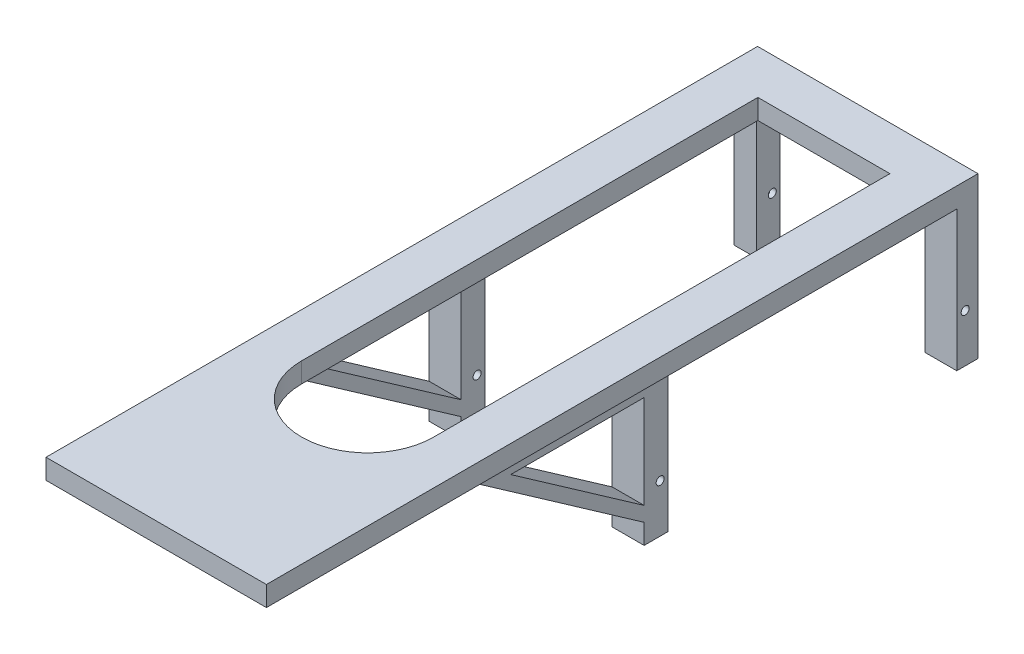
SolidWorks part; units mm, degrees
ref_plane "Plan de face" through (0, 0, 0) normal (0, 0, 1) x (1, 0, 0)
ref_plane "Plan de dessus" through (0, 0, 0) normal (0, 1, 0) x (1, 0, 0)
ref_plane "Plan de droite" through (0, 0, 0) normal (1, 0, 0) x (0, 0, -1)
sketch "Esquisse2" plane through (0, 0, 0) normal (0, 1, 0) x (1, 0, 0)
  line L0 (63.173, 102.455) -> (55.173, 102.455)
  line L1 (13.713, 101.825) -> (8.113, 101.825)
  line L2 (13.713, 101.825) -> (13.713, 107.755)
  line L3 (13.713, 107.755) -> (8.113, 107.755)
  line L4 (8.113, 101.825) -> (8.113, 107.755)
  line L5 (13.713, 101.825) -> (8.113, 107.755) construction
  line L6 (13.713, 107.755) -> (8.113, 101.825) construction
  line L7 (63.173, 102.455) -> (63.173, 107.755)
  line L8 (63.173, 107.755) -> (55.173, 107.755)
  line L9 (55.173, 102.455) -> (55.173, 107.755)
  line L10 (16.183, 25.625) -> (8.183, 25.625)
  line L11 (16.183, 25.625) -> (16.183, 31.625)
  line L12 (16.183, 31.625) -> (8.183, 31.625)
  line L13 (8.183, 25.625) -> (8.183, 31.625)
  line L14 (61.903, 25.625) -> (53.903, 25.625)
  line L15 (61.903, 25.625) -> (61.903, 31.625)
  line L16 (61.903, 31.625) -> (53.903, 31.625)
  line L17 (53.903, 25.625) -> (53.903, 31.625)
  circle A0 centre (12.183, 29.625) radius 1.6 construction
  circle A1 centre (57.903, 29.625) radius 1.6 construction
  circle A2 centre (10.913, 105.825) radius 1.6 construction
  circle A3 centre (59.173, 104.555) radius 1.6 construction
  point P8 (10.913, 104.79)
  dimension "D1" = 3.2
  dimension "D2" = 3.2
  dimension "D3" = 3.2
  dimension "D4" = 3.2
  dimension "D5" = 12.183
  dimension "D6" = 29.625
  dimension "D7" = 57.903
  dimension "D8" = 29.625
  dimension "D9" = 10.913
  dimension "D10" = 105.825
  dimension "D11" = 59.173
  dimension "D12" = 104.555
  dimension "D14" = 4
  dimension "D15" = 2.8
  dimension "D16" = 2.8
  dimension "D17" = 2.1
  dimension "D18" = 3.2
  dimension "D19" = 4
  dimension "D20" = 4
  dimension "D21" = 4
  dimension "D22" = 2
  dimension "D23" = 4
  dimension "D24" = 4
  dimension "D25" = 8
  dimension "D26" = 4
  dimension "D27" = 2
  dimension "D28" = 4
extrude "Boss.-Extru.1" add sketch "Esquisse2" along normal blind 35
ref_plane "Plan1" through (0, 35, 0) normal (0, 1, 0) x (1, 0, 0)
sketch "Esquisse3" plane through (0, 35, 0) normal (0, 1, 0) x (1, 0, 0)
  line L0 (13.713, 107.755) -> (8.113, 107.755) construction
  line L1 (63.173, -70) -> (8.113, -70)
  line L2 (63.173, -70) -> (63.173, 107.755)
  line L3 (63.173, 107.755) -> (8.113, 107.755)
  line L4 (8.113, -70) -> (8.113, 107.755)
  line L5 (63.173, -70) -> (8.113, 107.755) construction
  line L6 (63.173, 107.755) -> (8.113, -70) construction
  line L7 (8.113, 107.755) -> (8.113, 101.825) construction
  line L8 (63.173, 102.455) -> (63.173, 107.755) construction
  point P0 (35.643, 18.8775)
  dimension "D1" = 0
  dimension "D2" = 0
  dimension "D3" = 0
  dimension "D4" = 70
extrude "Boss.-Extru.2" add sketch "Esquisse3" along normal blind 5
ref_plane "Plan2" through (0, 0, -107.755) normal (0, 0, -1) x (-1, 0, 0)
sketch "Esquisse8" plane through (0, 35, 0) normal (0, 1, 0) x (1, 0, 0)
  line L0 (8.113, -70) -> (63.173, -70) construction
  line L1 (54.673, -69) -> (55.173, -69)
  line L2 (54.673, -69) -> (54.673, -44)
  line L3 (54.673, -44) -> (55.173, -44)
  line L4 (55.173, -69) -> (55.173, -44)
  line L5 (54.673, -69) -> (55.173, -44) construction
  line L6 (54.673, -44) -> (55.173, -69) construction
  line L7 (60.173, -69) -> (60.673, -69)
  line L8 (60.173, -69) -> (60.173, -44)
  line L9 (60.173, -44) -> (60.673, -44)
  line L10 (60.673, -69) -> (60.673, -44)
  line L11 (60.173, -69) -> (60.673, -44) construction
  line L12 (60.173, -44) -> (60.673, -69) construction
  line L26 (63.173, -70) -> (63.173, 102.455) construction
  line L27 (49.173, -69) -> (49.673, -69)
  line L28 (49.173, -69) -> (49.173, -44)
  line L29 (49.173, -44) -> (49.673, -44)
  line L30 (49.673, -69) -> (49.673, -44)
  line L31 (49.173, -69) -> (49.673, -44) construction
  line L32 (49.173, -44) -> (49.673, -69) construction
  line L33 (43.673, -69) -> (44.173, -69)
  line L34 (43.673, -69) -> (43.673, -44)
  line L35 (43.673, -44) -> (44.173, -44)
  line L36 (44.173, -69) -> (44.173, -44)
  line L37 (43.673, -69) -> (44.173, -44) construction
  line L38 (43.673, -44) -> (44.173, -69) construction
  line L39 (38.173, -69) -> (38.673, -69)
  line L40 (38.173, -69) -> (38.173, -44)
  line L41 (38.173, -44) -> (38.673, -44)
  line L42 (38.673, -69) -> (38.673, -44)
  line L43 (38.173, -69) -> (38.673, -44) construction
  line L44 (38.173, -44) -> (38.673, -69) construction
  line L45 (32.673, -69) -> (33.173, -69)
  line L46 (32.673, -69) -> (32.673, -44)
  line L47 (32.673, -44) -> (33.173, -44)
  line L48 (33.173, -69) -> (33.173, -44)
  line L49 (32.673, -69) -> (33.173, -44) construction
  line L50 (32.673, -44) -> (33.173, -69) construction
  line L51 (27.173, -69) -> (27.673, -69)
  line L52 (27.173, -69) -> (27.173, -44)
  line L53 (27.173, -44) -> (27.673, -44)
  line L54 (27.673, -69) -> (27.673, -44)
  line L55 (27.173, -69) -> (27.673, -44) construction
  line L56 (27.173, -44) -> (27.673, -69) construction
  line L57 (21.673, -69) -> (22.173, -69)
  line L58 (21.673, -69) -> (21.673, -44)
  line L59 (21.673, -44) -> (22.173, -44)
  line L60 (22.173, -69) -> (22.173, -44)
  line L61 (21.673, -69) -> (22.173, -44) construction
  line L62 (21.673, -44) -> (22.173, -69) construction
  line L63 (16.173, -69) -> (16.673, -69)
  line L64 (16.173, -69) -> (16.173, -44)
  line L65 (16.173, -44) -> (16.673, -44)
  line L66 (16.673, -69) -> (16.673, -44)
  line L67 (16.173, -69) -> (16.673, -44) construction
  line L68 (16.173, -44) -> (16.673, -69) construction
  line L69 (10.673, -69) -> (11.173, -69)
  line L70 (10.673, -69) -> (10.673, -44)
  line L71 (10.673, -44) -> (11.173, -44)
  line L72 (11.173, -69) -> (11.173, -44)
  line L73 (10.673, -69) -> (11.173, -44) construction
  line L74 (10.673, -44) -> (11.173, -69) construction
  point P0 (54.923, -56.5)
  point P5 (60.423, -56.5)
  point P10 (0, 0)
  point P23 (49.423, -56.5)
  point P30 (43.923, -56.5)
  point P35 (38.423, -56.5)
  point P40 (32.923, -56.5)
  point P45 (27.423, -56.5)
  point P50 (21.923, -56.5)
  point P55 (16.423, -56.5)
  point P60 (10.923, -56.5)
  dimension "D1" = 0.5
  dimension "D2" = 0.5
  dimension "D5" = 25
  dimension "D6" = 25
  dimension "D9" = 1
  dimension "D10" = 1
  dimension "D11" = 5
  dimension "D12" = 2.5
  dimension "D13" = 9
  dimension "D16" = 5
extrude "Enlèv. mat.-Extru.3" cut sketch "Esquisse8" along normal blind 3.5
sketch "Esquisse9" plane through (0, 35, 0) normal (0, 1, 0) x (1, 0, 0)
  line L0 (63.173, -70) -> (63.173, 102.455) construction
  line L1 (37.173, -65) -> (62.173, -65)
  line L2 (37.173, -65) -> (37.173, -64.5)
  line L3 (37.173, -64.5) -> (62.173, -64.5)
  line L4 (62.173, -65) -> (62.173, -64.5)
  line L5 (37.173, -65) -> (62.173, -64.5) construction
  line L6 (37.173, -64.5) -> (62.173, -65) construction
  line L7 (8.113, -70) -> (63.173, -70) construction
  line L8 (9.113, -65) -> (34.113, -65)
  line L9 (9.113, -65) -> (9.113, -64.5)
  line L10 (9.113, -64.5) -> (34.113, -64.5)
  line L11 (34.113, -65) -> (34.113, -64.5)
  line L12 (9.113, -65) -> (34.113, -64.5) construction
  line L13 (9.113, -64.5) -> (34.113, -65) construction
  line L14 (8.113, 101.825) -> (8.113, -70) construction
  line L15 (37.173, -62) -> (62.173, -62)
  line L16 (37.173, -62) -> (37.173, -61.5)
  line L17 (37.173, -61.5) -> (62.173, -61.5)
  line L18 (62.173, -62) -> (62.173, -61.5)
  line L19 (9.113, -62) -> (34.113, -62)
  line L20 (9.113, -62) -> (9.113, -61.5)
  line L21 (9.113, -61.5) -> (34.113, -61.5)
  line L22 (34.113, -62) -> (34.113, -61.5)
  line L23 (37.173, -62) -> (62.173, -61.5) construction
  line L24 (37.173, -61.5) -> (62.173, -62) construction
  line L25 (9.113, -62) -> (34.113, -61.5) construction
  line L26 (9.113, -61.5) -> (34.113, -62) construction
  line L27 (37.173, -59) -> (62.173, -59)
  line L28 (37.173, -59) -> (37.173, -58.5)
  line L29 (37.173, -58.5) -> (62.173, -58.5)
  line L30 (62.173, -59) -> (62.173, -58.5)
  line L31 (9.113, -59) -> (34.113, -59)
  line L32 (9.113, -59) -> (9.113, -58.5)
  line L33 (9.113, -58.5) -> (34.113, -58.5)
  line L34 (34.113, -59) -> (34.113, -58.5)
  line L35 (37.173, -59) -> (62.173, -58.5) construction
  line L36 (37.173, -58.5) -> (62.173, -59) construction
  line L37 (9.113, -59) -> (34.113, -58.5) construction
  line L38 (9.113, -58.5) -> (34.113, -59) construction
  line L39 (37.173, -56) -> (62.173, -56)
  line L40 (37.173, -56) -> (37.173, -55.5)
  line L41 (37.173, -55.5) -> (62.173, -55.5)
  line L42 (62.173, -56) -> (62.173, -55.5)
  line L43 (9.113, -56) -> (34.113, -56)
  line L44 (9.113, -56) -> (9.113, -55.5)
  line L45 (9.113, -55.5) -> (34.113, -55.5)
  line L46 (34.113, -56) -> (34.113, -55.5)
  line L47 (37.173, -56) -> (62.173, -55.5) construction
  line L48 (37.173, -55.5) -> (62.173, -56) construction
  line L49 (9.113, -56) -> (34.113, -55.5) construction
  line L50 (9.113, -55.5) -> (34.113, -56) construction
  line L51 (37.173, -53) -> (62.173, -53)
  line L52 (37.173, -53) -> (37.173, -52.5)
  line L53 (37.173, -52.5) -> (62.173, -52.5)
  line L54 (62.173, -53) -> (62.173, -52.5)
  line L55 (9.113, -53) -> (34.113, -53)
  line L56 (9.113, -53) -> (9.113, -52.5)
  line L57 (9.113, -52.5) -> (34.113, -52.5)
  line L58 (34.113, -53) -> (34.113, -52.5)
  line L59 (37.173, -53) -> (62.173, -52.5) construction
  line L60 (37.173, -52.5) -> (62.173, -53) construction
  line L61 (9.113, -53) -> (34.113, -52.5) construction
  line L62 (9.113, -52.5) -> (34.113, -53) construction
  line L63 (37.173, -50) -> (62.173, -50)
  line L64 (37.173, -50) -> (37.173, -49.5)
  line L65 (37.173, -49.5) -> (62.173, -49.5)
  line L66 (62.173, -50) -> (62.173, -49.5)
  line L67 (9.113, -50) -> (34.113, -50)
  line L68 (9.113, -50) -> (9.113, -49.5)
  line L69 (9.113, -49.5) -> (34.113, -49.5)
  line L70 (34.113, -50) -> (34.113, -49.5)
  line L71 (37.173, -50) -> (62.173, -49.5) construction
  line L72 (37.173, -49.5) -> (62.173, -50) construction
  line L73 (9.113, -50) -> (34.113, -49.5) construction
  line L74 (9.113, -49.5) -> (34.113, -50) construction
  line L75 (37.173, -47) -> (62.173, -47)
  line L76 (37.173, -47) -> (37.173, -46.5)
  line L77 (37.173, -46.5) -> (62.173, -46.5)
  line L78 (62.173, -47) -> (62.173, -46.5)
  line L79 (9.113, -47) -> (34.113, -47)
  line L80 (9.113, -47) -> (9.113, -46.5)
  line L81 (9.113, -46.5) -> (34.113, -46.5)
  line L82 (34.113, -47) -> (34.113, -46.5)
  line L83 (37.173, -47) -> (62.173, -46.5) construction
  line L84 (37.173, -46.5) -> (62.173, -47) construction
  line L85 (9.113, -47) -> (34.113, -46.5) construction
  line L86 (9.113, -46.5) -> (34.113, -47) construction
  point P0 (49.673, -64.75)
  point P10 (21.613, -64.75)
  point P17 (49.673, -61.75)
  point P22 (21.613, -61.75)
  point P27 (49.673, -58.75)
  point P32 (21.613, -58.75)
  point P37 (49.673, -55.75)
  point P42 (21.613, -55.75)
  point P47 (49.673, -52.75)
  point P52 (21.613, -52.75)
  point P57 (49.673, -49.75)
  point P62 (21.613, -49.75)
  point P67 (49.673, -46.75)
  point P72 (21.613, -46.75)
  dimension "D1" = 1
  dimension "D2" = 0.5
  dimension "D3" = 5
  dimension "D4" = 25
  dimension "D6" = 1
  dimension "D7" = 25
  dimension "D9" = 2.5
  dimension "D5" = 2
  dimension "D8" = 7
extrude "Enlèv. mat.-Extru.4" cut sketch "Esquisse9" along normal blind 3.5
ref_plane "Plan5" through (61.903, 0, 0) normal (1, 0, 0) x (0, 0, -1)
ref_plane "Plan6" through (8.183, 0, 0) normal (-1, 0, 0) x (0, 0, 1)
sketch "Esquisse13" plane through (61.903, 0, 0) normal (1, 0, 0) x (0, 0, -1)
  line L0 (25.625, 5) -> (-17.2194, 35)
  line L1 (25.625, 35) -> (25.625, 0) construction
  line L2 (77.2769, 35) -> (-77.2769, 35) construction
  line L3 (-17.2194, 35) -> (25.625, 35)
  line L4 (25.625, 35) -> (25.625, 5)
  line L5 (25.625, 0) -> (31.625, 0) construction
  point P9 (-19.763, 35)
  point P11 (-28.9781, 35)
  dimension "D1" = 55
  dimension "D2" = 5
extrude "Boss.-Extru.3" add sketch "Esquisse13" against normal blind 8
sketch "Esquisse14" plane through (8.183, 0, 0) normal (-1, 0, 0) x (0, 0, 1)
  line L0 (-25.625, 5) -> (17.2194, 35)
  line L1 (77.2769, 35) -> (-77.2769, 35) construction
  line L2 (-101.825, 35) -> (70, 35) construction
  line L3 (17.2194, 35) -> (-25.625, 35)
  line L4 (-25.625, 35) -> (-25.625, 0) construction
  line L5 (-25.625, 35) -> (-25.625, 5)
  dimension "D1" = 55
extrude "Boss.-Extru.4" add sketch "Esquisse14" against normal blind 8
ref_plane "Plan7" through (0, 0, 0) normal (0, -1, 0) x (-1, 0, 0)
sketch "Esquisse15" plane through (0, 0, 0) normal (0, -1, 0) x (-1, 0, 0)
  circle A0 centre (-12.183, 29.625) radius 1.6
  circle A1 centre (-57.903, 29.625) radius 1.6
  circle A2 centre (-10.913, 105.825) radius 1.6
  circle A3 centre (-59.173, 104.555) radius 1.6
  point P45 (0, 0)
  point P46 (0, 0)
  point P47 (-16.983, 24.825)
  point P48 (-16.983, 24.825)
  point P49 (0, 0)
  dimension "D2" = 3.2
  dimension "D3" = 3.2
  dimension "D4" = 3.2
  dimension "D5" = 3.2
  dimension "D1" = 12.183
  dimension "D6" = 29.625
  dimension "D7" = 29.625
  dimension "D8" = 57.903
  dimension "D9" = 105.825
  dimension "D10" = 10.913
  dimension "D11" = 104.555
  dimension "D12" = 59.173
extrude "Enlèv. mat.-Extru.5" cut sketch "Esquisse15" against normal blind 15
sketch "Esquisse16" plane through (8.113, 0, 0) normal (-1, 0, 0) x (0, 0, 1)
  line L2 (-35.6275, 0) -> (35.6275, 0) construction
  circle A0 centre (-105.825, 12) radius 1
  dimension "D3" = 2
  dimension "D1" = 105.825
  dimension "D4" = 12
extrude "Enlèv. mat.-Extru.6" cut sketch "Esquisse16" against normal blind 9.6
sketch "Esquisse18" plane through (63.173, 0, 0) normal (1, 0, 0) x (0, 0, -1)
  line L0 (-35.6275, 0) -> (35.6275, 0) construction
  circle A0 centre (104.555, 12) radius 1
  dimension "D2" = 2
  dimension "D1" = 12
  dimension "D3" = 104.555
extrude "Enlèv. mat.-Extru.7" cut sketch "Esquisse18" against normal blind 9.6
sketch "Esquisse19" plane through (8.183, 0, 0) normal (-1, 0, 0) x (0, 0, 1)
  line L1 (-35.6275, 0) -> (35.6275, 0) construction
  line L2 (-25.625, 8.6623) -> (7.7047, 32)
  line L3 (7.7047, 32) -> (-25.625, 32)
  line L4 (-25.625, 32) -> (-25.625, 8.6623)
  line L5 (-25.625, 5) -> (-25.625, 0) construction
  line L6 (-101.825, 35) -> (70, 35) construction
  line L7 (-25.625, 5) -> (17.2194, 35) construction
  circle A0 centre (-29.625, 12) radius 1
  point P9 (-23.9951, 32.5089)
  dimension "D1" = 2
  dimension "D2" = 29.625
  dimension "D3" = 12
  dimension "D4" = 0
  dimension "D5" = 3
  dimension "D7" = 3
extrude "Enlèv. mat.-Extru.8" cut sketch "Esquisse19" against normal through all
sketch "Esquisse20" plane through (0, 40, 0) normal (0, 1, 0) x (1, 0, 0)
  line L0 (44.712, 107.755) -> (-44.712, 107.755) construction
  line L1 (19.183, 96.755) -> (52.173, 96.755)
  line L2 (19.183, 96.755) -> (19.183, -17.2194)
  line L4 (52.173, 96.755) -> (52.173, -17.2194)
  line L5 (19.183, 96.755) -> (52.173, -17.2194) construction
  line L6 (19.183, -17.2194) -> (52.173, 96.755) construction
  line L7 (8.183, 110.1157) -> (8.183, -110.1157) construction
  line L8 (63.173, -70) -> (63.173, 107.755) construction
  arc A0 (19.183, -17.2194) -> (52.173, -17.2194) centre (35.678, -17.2194) ccw
  point P0 (35.678, 39.7678)
  dimension "D4" = 0
  dimension "D1" = 11
  dimension "D2" = 11
  dimension "D3" = 11
extrude "Enlèv. mat.-Extru.9" cut sketch "Esquisse20" against normal up to next
